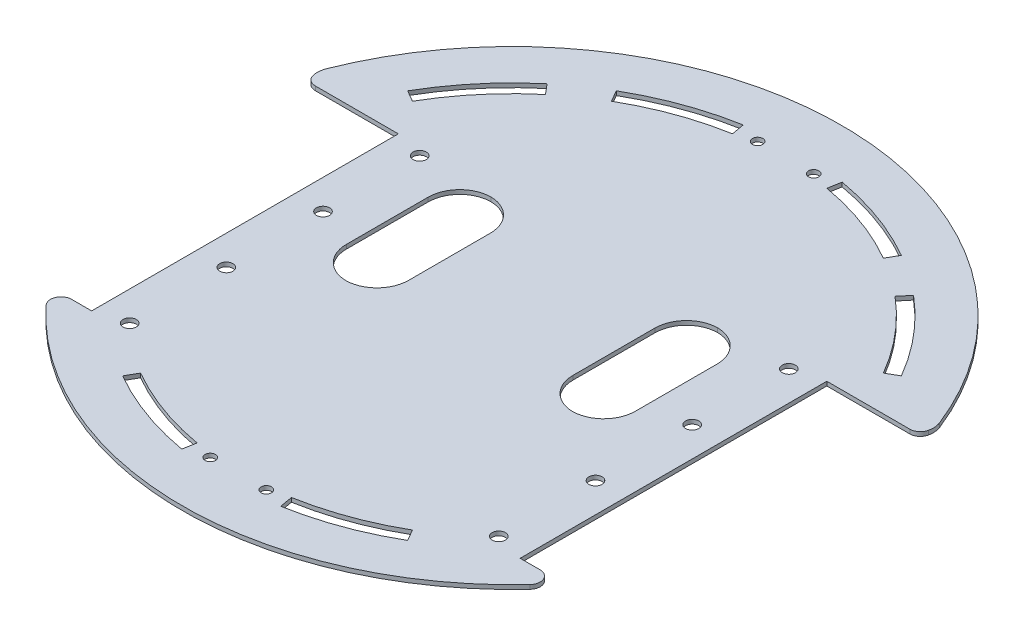
SolidWorks part; units mm, degrees
ref_plane "Front Plane" through (0, 0, 0) normal (0, 0, 1) x (1, 0, 0)
ref_plane "Top Plane" through (0, 0, 0) normal (0, 1, 0) x (1, 0, 0)
ref_plane "Right Plane" through (0, 0, 0) normal (1, 0, 0) x (0, 0, -1)
sketch "Sketch1" plane through (0, 0, 0) normal (0, 1, 0) x (1, 0, 0)
  line L0 (0, 0) -> (0, -79.375)
  line L1 (7.1438, -66.675) -> (-7.1437, -66.675)
  line L2 (50.8, 22.225) -> (76.2, 22.225)
  line L3 (-63.5, -47.625) -> (-50.8, -47.625)
  line L4 (-50.8, -47.625) -> (-50.8, 22.225)
  line L5 (63.5, -47.625) -> (50.8, -47.625)
  line L6 (50.8, -47.625) -> (50.8, 22.225)
  line L7 (-50.8, 22.225) -> (-76.2, 22.225)
  line L8 (0, 0) -> (-27.2811, 0)
  circle A0 centre (0, 0) radius 79.375
  circle A1 centre (-7.1437, -66.675) radius 1.5875
  circle A2 centre (7.1438, -66.675) radius 1.5875
  circle A3 centre (7.1438, 66.675) radius 1.5875
  circle A4 centre (-7.1437, 66.675) radius 1.5875
  point P7 (0, -66.675)
  dimension "D1" = 7.1437
  dimension "D3" = 50.8
  dimension "D6" = 3.175
  dimension "D2" = 12.7
  dimension "D4" = 69.85
  dimension "D5" = 47.625
extrude "Boss-Extrude5" add sketch "Sketch1" along normal blind 1.5875 contours A2 A0 L5 L6 L2 L7 L4 L3 A1 A3 region at (0, 0, -2.0947)
fillet "Fillet2" radius 2.54 1 edges at (-63.5, 0.7937, 47.625)
fillet "Fillet3" radius 2.54 1 edges at (63.5, 0.7937, 47.625)
fillet "Fillet4" radius 5.08 2 edges at (-76.2, 0.7937, -22.225) (76.2, 0.7937, -22.225)
sketch "Sketch2" plane through (0, 1.5875, 0) normal (0, 1, 0) x (1, 0, 0)
  line L0 (0, 0) -> (0, 79.375)
  line L1 (0, 0) -> (-67.0566, 0)
  line L2 (0, 0) -> (-61.0886, 27.6545)
  line L3 (0, 0) -> (-43.6778, 50.8806)
  line L4 (0, 0) -> (-63.2664, 22.225)
  line L5 (-50.8, 22.225) -> (-69.0955, 22.225) construction
  line L6 (0, 0) -> (0, 2.6153)
  line L7 (0, 0) -> (-39.0771, 54.4938)
  line L8 (0, 0) -> (-12.3858, 65.9028)
  line L9 (-62.5348, 28.3092) -> (-59.6424, 26.9998)
  line L10 (-43.6778, 50.8806) -> (-44.7118, 52.0852)
  line L11 (-43.6778, 50.8806) -> (-42.6438, 49.6761)
  line L12 (-39.0771, 54.4938) -> (-40.0022, 55.7839)
  line L13 (-39.0771, 54.4938) -> (-38.152, 53.2037)
  line L14 (-43.6778, 50.8806) -> (-42.6438, 49.6761)
  line L15 (-12.3858, 65.9028) -> (-12.0926, 64.3426)
  line L16 (-12.3858, 65.9028) -> (-12.679, 67.463)
  line L17 (61.5813, 22.225) -> (64.9466, 22.225)
  line L18 (50.8, 22.225) -> (69.0955, 22.225) construction
  line L19 (12.3858, 65.9028) -> (12.679, 67.463)
  line L20 (12.3858, 65.9028) -> (12.0926, 64.3426)
  line L21 (39.0771, 54.4938) -> (38.152, 53.2037)
  line L22 (43.6778, 50.8806) -> (42.6438, 49.6761)
  line L23 (39.0771, 54.4938) -> (40.0022, 55.7839)
  line L24 (43.6778, 50.8806) -> (42.6438, 49.6761)
  line L25 (43.6778, 50.8806) -> (44.7118, 52.0852)
  line L26 (62.5348, 28.3092) -> (59.6424, 26.9998)
  line L27 (-50.8, -41.2985) -> (-50.8, -43.7716)
  line L28 (-50.8, -47.625) -> (-50.8, 22.225) construction
  line L29 (50.8, -41.2985) -> (50.8, -46.1668)
  line L30 (50.8, -47.625) -> (50.8, 22.225) construction
  line L31 (39.0771, -54.4938) -> (40.0022, -55.7839)
  line L32 (39.0771, -54.4938) -> (38.152, -53.2037)
  line L33 (12.3858, -65.9028) -> (12.0926, -64.3426)
  line L34 (12.3858, -65.9028) -> (12.679, -67.463)
  line L35 (-12.3858, -65.9028) -> (-12.679, -67.463)
  line L36 (-12.3858, -65.9028) -> (-12.0926, -64.3426)
  line L37 (-39.0771, -54.4938) -> (-38.152, -53.2037)
  line L38 (-39.0771, -54.4938) -> (-40.0022, -55.7839)
  arc A0 (-63.2664, 22.225) -> (-50.8, -43.7716) centre (0, 0) ccw
  arc A1 (73.8199, 29.172) -> (-73.8199, 29.172) centre (0, 0) ccw construction
  circle A2 centre (-7.1437, 66.675) radius 2.3813
  circle A3 centre (7.1437, 66.675) radius 2.3813
  circle A4 centre (7.1437, -66.675) radius 2.3813
  circle A5 centre (-7.1437, -66.675) radius 2.3813
  arc A6 (12.679, -67.463) -> (40.0022, -55.7839) centre (0, 0) ccw
  arc A7 (-61.7686, 21.6988) -> (-50.8, -41.2985) centre (0, 0) ccw
  arc A8 (-44.7118, 52.0852) -> (-62.5348, 28.3092) centre (0, 0) ccw
  arc A9 (-42.6438, 49.6761) -> (-59.6424, 26.9998) centre (0, 0) ccw
  arc A10 (12.0926, 64.3426) -> (38.152, 53.2037) centre (0, 0) cw
  arc A11 (12.679, 67.463) -> (40.0022, 55.7839) centre (0, 0) cw
  arc A12 (42.6438, 49.6761) -> (59.6424, 26.9998) centre (0, 0) cw
  arc A13 (-12.679, 67.463) -> (-40.0022, 55.7839) centre (0, 0) ccw
  arc A14 (44.7118, 52.0852) -> (62.5348, 28.3092) centre (0, 0) cw
  arc A15 (-12.0926, 64.3426) -> (-38.152, 53.2037) centre (0, 0) ccw
  arc A16 (12.0926, -64.3426) -> (38.152, -53.2037) centre (0, 0) ccw
  arc A17 (-12.0926, -64.3426) -> (-38.152, -53.2037) centre (0, 0) cw
  arc A18 (50.8, -46.1668) -> (64.9466, 22.225) centre (0, 0) ccw
  arc A19 (50.8, -43.7716) -> (63.2664, 22.225) centre (0, 0) ccw
  arc A20 (50.8, -41.2985) -> (61.5813, 22.225) centre (0, 0) ccw
  arc A21 (-12.679, -67.463) -> (-40.0022, -55.7839) centre (0, 0) cw
  circle M13 centre (-7.1437, -66.675) radius 1.5875
  circle M14 centre (7.1438, -66.675) radius 1.5875
  circle M15 centre (7.1438, 66.675) radius 1.5875
  circle M16 centre (-7.1437, 66.675) radius 1.5875
  dimension "D2" = 4.7625
  dimension "D7" = 1.5875
  dimension "D8" = 3.175
  dimension "D1" = 5
  dimension "D3" = 25
  dimension "D4" = 5
  dimension "D5" = 25
extrude "Cut-Extrude1" cut sketch "Sketch2" against normal blind 2.54 contours A9 L3 L10 A8 L9 L2 | A15 L8 L16 A13 L12 L7 | A2 M16 | A3 M15 | A11 L19 L20 A10 L21 L23 | A14 L25 L22 A12 L26 | A21 L35 L36 A17 L37 L38 | A5 M13 | A4 M14 | A16 L33 L34 A6 L31 L32 region at (-53.2404, 1.5875, -39.9101) region at (-26.1525, 1.5875, -61.1833) region at (26.1525, 1.5875, -61.1833) region at (53.2404, 1.5875, -39.9101) region at (26.1525, 1.5875, 61.1833) region at (-26.1525, 1.5875, 61.1833) region at (-9.4576, 1.5875, -66.675) region at (4.8299, 1.5875, -66.675) region at (4.8299, 1.5875, 66.675) region at (-9.4576, 1.5875, 66.675)
sketch "Sketch3" plane through (0, 1.5875, 0) normal (0, 1, 0) x (1, 0, 0)
  line L0 (-50.8, 22.225) -> (-50.8, -47.625)
  line L1 (-50.8, -47.625) -> (-44.45, -47.625)
  line L2 (-50.8, 22.225) -> (-44.45, 22.225)
  line L3 (0, 0) -> (0, 32.9013)
  circle A0 centre (-44.45, -47.625) radius 1.5875
  circle A1 centre (-44.45, 22.225) radius 1.5875
  circle A2 centre (44.45, 22.225) radius 1.5875
  circle A3 centre (44.45, -47.625) radius 1.5875
  dimension "D2" = 3.175
  dimension "D4" = 3.175
  dimension "D1" = 6.35
  dimension "D3" = 6.35
extrude "Cut-Extrude2" cut sketch "Sketch3" against normal blind 2.54 contours A1 | A2 | A0 | A3 region at (-44.45, 1.5875, 46.0824) region at (-44.45, 1.5875, -23.7676) region at (44.45, 1.5875, -22.225) region at (44.45, 1.5875, 47.625)
sketch "Sketch4" plane through (0, 1.5875, 0) normal (0, 1, 0) x (1, 0, 0)
  line L0 (-44.45, -47.625) -> (-44.45, 22.225)
  line L1 (-44.45, 22.225) -> (-50.8, 22.225)
  line L2 (-50.8, -47.625) -> (-50.8, 22.225) construction
  line L3 (0, 0) -> (0, -67.5878)
  line L4 (44.45, -47.625) -> (44.45, 22.225)
  circle A0 centre (-44.45, 22.225) radius 1.5875
  circle A1 centre (-44.45, -12.7) radius 1.5875
  circle A2 centre (44.45, -12.7) radius 1.5875
  dimension "D2" = 3.175
  dimension "D1" = 69.85
extrude "Cut-Extrude3" cut sketch "Sketch4" against normal blind 2.54 contours L0 A1 | L0 A1 | A2 L4 | A2 L4 region at (-45.1238, 1.5875, 12.7) region at (-43.7762, 1.5875, 12.7) region at (43.7762, 1.5875, 12.7) region at (45.1238, 1.5875, 12.7)
sketch "Sketch5" plane through (0, 1.5875, 0) normal (0, 1, 0) x (1, 0, 0)
  line L0 (-50.8, -12.7) -> (-34.8, -12.7)
  line L1 (-50.8, -47.625) -> (-50.8, 22.225) construction
  line L2 (-50.8, 22.225) -> (-34.8, 22.225)
  line L3 (-34.8, 22.225) -> (-34.8, -12.7)
  line L4 (0, 0) -> (0, 64.5379)
  line L5 (-34.8, 22.225) -> (-19.8, 22.225)
  line L6 (-19.8, 22.225) -> (-19.8, -12.7)
  line L7 (-19.8, -12.7) -> (-34.8, -12.7)
  line L8 (19.8, -12.7) -> (34.8, -12.7)
  line L9 (19.8, 22.225) -> (19.8, -12.7)
  line L10 (34.8, 22.225) -> (19.8, 22.225)
  line L11 (34.8, 22.225) -> (34.8, -12.7)
  dimension "D1" = 16
  dimension "D2" = 16
extrude "Cut-Extrude4" cut sketch "Sketch5" against normal through all contours L7 L6 L5 L3 | L11 L10 L9 L8 region at (-27.3, 1.5875, -4.7625) region at (27.3, 1.5875, -4.7625)
fillet "Fillet5" radius 7.62 4 edges at (-19.8, 0.7937, 12.7) (-34.8, 0.7937, 12.7) (-19.8, 0.7937, -22.225) (-34.8, 0.7937, -22.225)
fillet "Fillet6" radius 7.62 4 edges at (34.8, 0.7937, 12.7) (34.8, 0.7937, -22.225) (19.8, 0.7937, -22.225) (19.8, 0.7937, 12.7)
sketch "Sketch6" plane through (0, 0, 0) normal (0, -1, 0) x (-1, 0, 0)
  circle A0 centre (0, 0) radius 79.375
extrude "Cut-Extrude5" cut sketch "Sketch6" against normal blind 0.5875
sketch "Sketch8" plane through (0, 1.5875, 0) normal (0, 1, 0) x (1, 0, 0)
  line L0 (-50.8, 22.225) -> (-50.8, 24.225)
  line L1 (-50.8, 24.225) -> (-80.2365, 24.225)
  line L2 (0, 0) -> (0, 19.3161)
  line L3 (0, 0) -> (-9.6505, 0)
  line L4 (50.8, 24.225) -> (80.2365, 24.225)
  line L5 (50.8, 22.225) -> (50.8, 24.225)
  line L6 (-50.8, -47.625) -> (-50.8, -49.625)
  line L7 (-50.8, -49.625) -> (-75.4506, -49.625)
  line L8 (50.8, -49.625) -> (75.4506, -49.625)
  line L9 (50.8, -47.625) -> (50.8, -49.625)
  line L10 (-50.8, -47.625) -> (-75.4506, -47.625)
  line L11 (-75.4506, -47.625) -> (-75.4506, -49.625)
  line L12 (50.8, -47.625) -> (75.4506, -47.625)
  line L13 (75.4506, -49.625) -> (75.4506, -47.625)
  line L14 (50.8, 22.225) -> (80.2365, 22.225)
  line L15 (80.2365, 22.225) -> (80.2365, 24.225)
  line L16 (-50.8, 22.225) -> (-80.2365, 22.225)
  line L17 (-80.2365, 22.225) -> (-80.2365, 24.225)
extrude "Cut-Extrude6" cut sketch "Sketch8" against normal blind 2.54 contours L10 L11 L7 L6 | L8 L13 L12 L9 | L14 L15 L4 L5 | L1 L17 L16 L0 region at (65.5183, 1.5875, -23.225) region at (-63.1253, 1.5875, 48.625) region at (63.1253, 1.5875, 48.625)
fillet "Fillet7" radius 2.54 4 edges at (-60.6806, 1.0875, 49.625) (60.6806, 1.0875, 49.625) (73.1353, 1.0875, -24.225) (-73.1353, 1.0875, -24.225)
sketch "Sketch11" plane through (0, 1.5875, 0) normal (0, 1, 0) x (1, 0, 0)
  line L1 (-11.0583, 60.7829) -> (11.2037, 60.7829)
  line L2 (-11.0583, 60.7829) -> (-11.0583, 72.1091)
  line L3 (-11.0583, 72.1091) -> (11.2037, 72.1091)
  line L4 (11.2037, 60.7829) -> (11.2037, 72.1091)
  line L5 (-11.0583, -61.658) -> (11.2037, -61.658)
  line L6 (-11.0583, -61.658) -> (-11.0583, -72.2032)
  line L7 (-11.0583, -72.2032) -> (11.2037, -72.2032)
  line L8 (11.2037, -61.658) -> (11.2037, -72.2032)
extrude "Boss-Extrude7" add sketch "Sketch11" against normal up to surface (1 mm away) up to face at (0, 0.5875, 5.2491)
sketch "Sketch12" plane through (0, 1.5875, 0) normal (0, 1, 0) x (1, 0, 0)
  line L0 (0, 0) -> (0, 79.375)
  line L1 (0, 0) -> (-6.75, 0)
  line L4 (0, 65.9028) -> (-6.75, 65.9028)
  line L5 (0, -65.9028) -> (-6.75, -65.9028)
  line L6 (-12.3858, -65.9028) -> (12.3858, -65.9028)
  line L7 (-12.0926, -64.3426) -> (-12.679, -67.463) construction
  line L8 (12.679, -67.463) -> (12.0926, -64.3426) construction
  arc A0 (73.8199, 29.172) -> (-73.8199, 29.172) centre (0, 0) ccw construction
  circle A1 centre (-6.75, 65.9028) radius 1.25
  circle A2 centre (6.75, 65.9028) radius 1.25
  circle A3 centre (6.75, -65.9028) radius 1.25
  circle A4 centre (-6.75, -65.9028) radius 1.25
  dimension "D1" = 2.5
  dimension "D2" = 13.5
extrude "Cut-Extrude7" cut sketch "Sketch12" against normal blind 2.54 contours A4 L6 | A4 L6 | L6 A3 | L6 A3 | A1 | A2 region at (-6.75, 1.5875, 66.4333) region at (-6.75, 1.5875, 65.3723) region at (6.75, 1.5875, 65.3723) region at (6.75, 1.5875, 66.4333) region at (-7.9646, 1.5875, -65.9028) region at (6.75, 1.5875, -65.9028)
sketch "Sketch14" plane through (0, 1.5875, 0) normal (0, 1, 0) x (1, 0, 0)
  circle A0 centre (-44.45, -12.7) radius 1.5875
  circle A2 centre (44.45, -12.7) radius 1.5875
  dimension "D1" = 3.175
extrude "Boss-Extrude8" add sketch "Sketch14" against normal up to surface (1 mm away) up to face at (-6.75, 0.5875, 64.6528)
sketch "Sketch15" plane through (0, 1.5875, 0) normal (0, 1, 0) x (1, 0, 0)
  line L0 (-44.45, 22.225) -> (-44.45, -1.0583)
  line L1 (-44.45, -1.0583) -> (-44.45, -24.3417)
  line L2 (0, 0) -> (0, 10.0728)
  line L3 (44.45, -1.0583) -> (44.45, -24.3417)
  circle A0 centre (-44.45, -1.0583) radius 1.5875
  circle A1 centre (-44.45, -24.3417) radius 1.5875
  circle A2 centre (44.45, -24.3417) radius 1.5875
  circle A3 centre (44.45, -1.0583) radius 1.5875
  dimension "D1" = 23.2833
  dimension "D2" = 3.175
  dimension "D3" = 23.2833
extrude "Cut-Extrude8" cut sketch "Sketch15" against normal blind 2.54 contours L1 A0 L0 | L0 A0 L1 | A1 | A2 | A3 region at (-43.7762, 1.5875, 1.0583) region at (-43.3592, 1.5875, 23.2509) region at (-45.1238, 1.5875, 1.0583) region at (45.5408, 1.5875, 23.2509) region at (43.3592, 1.5875, -0.0324)
sketch "Sketch16" plane through (0, 1.5875, 0) normal (0, 1, 0) x (1, 0, 0)
  line L0 (-44.45, -1.0583) -> (-51.5937, -1.0583)
  line L1 (-50.8, -49.625) -> (-56.413, -49.625) construction
  line L2 (-50.8, 24.225) -> (-51.5937, 24.225)
  line L3 (-50.8, 24.225) -> (-50.8, -49.625)
  line L4 (-50.8, -49.625) -> (-51.5937, -49.625)
  line L5 (-51.5937, 24.225) -> (-51.5937, -49.625)
  line L6 (0, 0) -> (0, 12.3631)
  line L7 (51.5937, 24.225) -> (51.5937, -49.625)
  line L8 (50.8, -49.625) -> (51.5937, -49.625)
  line L9 (50.8, 24.225) -> (50.8, -49.625)
  line L10 (50.8, 24.225) -> (51.5937, 24.225)
extrude "Boss-Extrude13" add sketch "Sketch16" against normal up to surface (1 mm away) contours L2 L5 L0 L3 | L0 L5 L4 L3 | L10 L9 L8 L7 region at (-51.1969, 1.5875, 25.3417) region at (-51.1969, 1.5875, -11.5833) region at (51.1969, 1.5875, 12.7) up to face at (44.45, 0.5875, 22.7542)
sketch "Sketch17" plane through (0, 1.5875, 0) normal (0, 1, 0) x (1, 0, 0)
  line L0 (0, 0) -> (0, 79.375)
  line L1 (0, 0) -> (-11.9199, 67.6013)
  line L2 (0, 0) -> (12.0176, 0)
  line L3 (0, 0) -> (-62.5348, 28.3092)
  line L4 (0, 0) -> (11.9199, 67.6013)
  line L5 (0, 0) -> (62.5348, 28.3092)
  line L6 (0, 0) -> (-40.0022, -55.7839)
  line L7 (0, 0) -> (11.9199, -67.6013)
  line L8 (0, 0) -> (-11.9199, -67.6013)
  line L9 (0, 0) -> (40.0022, -55.7839)
  arc A0 (73.8199, 29.172) -> (-73.8199, 29.172) centre (0, 0) ccw construction
  circle A1 centre (0, 0) radius 68.6441
  circle A2 centre (0, 0) radius 65.4691
  dimension "D1" = 10
extrude "Cut-Extrude10" cut sketch "Sketch17" against normal through all contours A2 L1 A1 L3 | A2 L5 A1 L4 | A2 L7 A1 L9 | A2 L6 A1 L8 region at (-40.5469, 1.5875, -52.2313) region at (12.2875, 1.5875, -65.9244) region at (-25.7975, 1.5875, 61.3039) region at (25.7975, 1.5875, 61.3039)
sketch "Sketch18" plane through (0, 1.5875, 0) normal (0, 1, 0) x (1, 0, 0)
  line L0 (0, 0) -> (0, 79.375)
  line L1 (0, 0) -> (-26.9517, 0)
  line L2 (0, 0) -> (-11.9199, 67.6013)
  line L3 (0, 0) -> (-34.3221, 59.4475)
  line L4 (0, 0) -> (-44.1236, 52.5844)
  line L5 (0, 0) -> (-59.4475, 34.3221)
  line L6 (-62.5348, 28.3092) -> (-59.6424, 26.9998)
  line L7 (0, 0) -> (11.9199, 67.6013)
  line L8 (0, 0) -> (34.3221, 59.4475)
  line L9 (0, 0) -> (44.1236, 52.5844)
  line L10 (0, 0) -> (59.4475, 34.3221)
  line L11 (0, 0) -> (44.1236, -52.5844)
  line L12 (0, 0) -> (-44.1236, -52.5844)
  line L13 (0, 0) -> (34.3221, -59.4475)
  line L14 (0, 0) -> (11.9199, -67.6013)
  line L15 (0, 0) -> (-11.9199, -67.6013)
  line L16 (0, 0) -> (-34.3221, -59.4475)
  line L17 (59.6424, 26.9998) -> (62.5348, 28.3092)
  line L18 (40.0022, -55.7839) -> (38.152, -53.2037)
  line L19 (-38.152, -53.2037) -> (-40.0022, -55.7839)
  arc A0 (73.8199, 29.172) -> (-73.8199, 29.172) centre (0, 0) ccw construction
  circle A1 centre (0, 0) radius 68.6441
  circle A2 centre (0, 0) radius 65.4691
  dimension "D1" = 20
  dimension "D2" = 10
  dimension "D3" = 20
extrude "Boss-Extrude16" add sketch "Sketch18" against normal up to surface (1 mm away) contours A2 L19 A1 L16 | A2 L13 A1 L18 | A2 L17 A1 L10 | A2 L9 A1 L8 | A2 L3 A1 L4 | A2 L5 A1 L6 region at (-38.4205, 1.5875, -54.8701) region at (-59.64, 1.5875, -30.6219) region at (38.4205, 1.5875, -54.8701) region at (59.64, 1.5875, -30.6219) region at (36.3389, 1.5875, 56.3393) region at (-36.3389, 1.5875, 56.3393) up to face at (25.6849, 0.5875, 61.0364)
